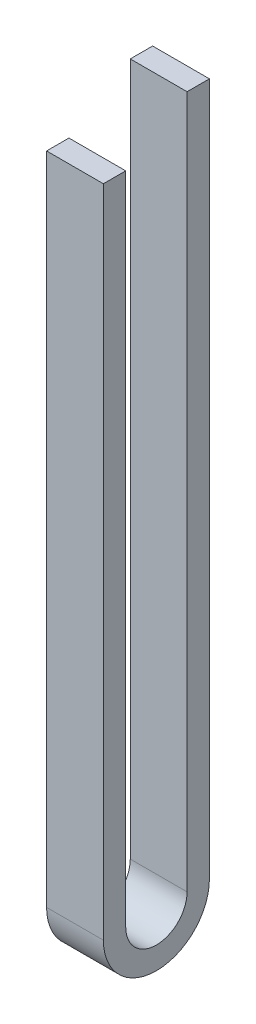
SolidWorks part; units mm, degrees
ref_plane "Front" through (0, 0, 0) normal (0, 0, 1) x (1, 0, 0)
ref_plane "Top" through (0, 0, 0) normal (0, 1, 0) x (1, 0, 0)
ref_plane "Right" through (0, 0, 0) normal (1, 0, 0) x (0, 0, -1)
sketch "Sketch1" plane through (0, 0, 0) normal (1, 0, 0) x (0, 0, -1)
  line L0 (0, 0) -> (0, -439.4425)
  line L1 (71.12, -439.4425) -> (71.12, 25.4)
  line L2 (14.986, 0) -> (14.986, -439.4425)
  line L3 (56.134, -439.4425) -> (56.134, 25.4)
  line L4 (0, 0) -> (14.986, 0)
  line L5 (56.134, 25.4) -> (71.12, 25.4)
  line L7 (23.876, 25.4) -> (107.061, 25.4) construction
  arc A0 (0, -439.4425) -> (71.12, -439.4425) centre (35.56, -439.4425) ccw
  arc A1 (14.986, -439.4425) -> (56.134, -439.4425) centre (35.56, -439.4425) ccw
  dimension "D1" = 1016
  dimension "D2" = 71.12
  dimension "D4" = 41.148
  dimension "D3" = 14.986
extrude "Boss-Extrude1" add sketch "Sketch1" along normal blind 38.1
